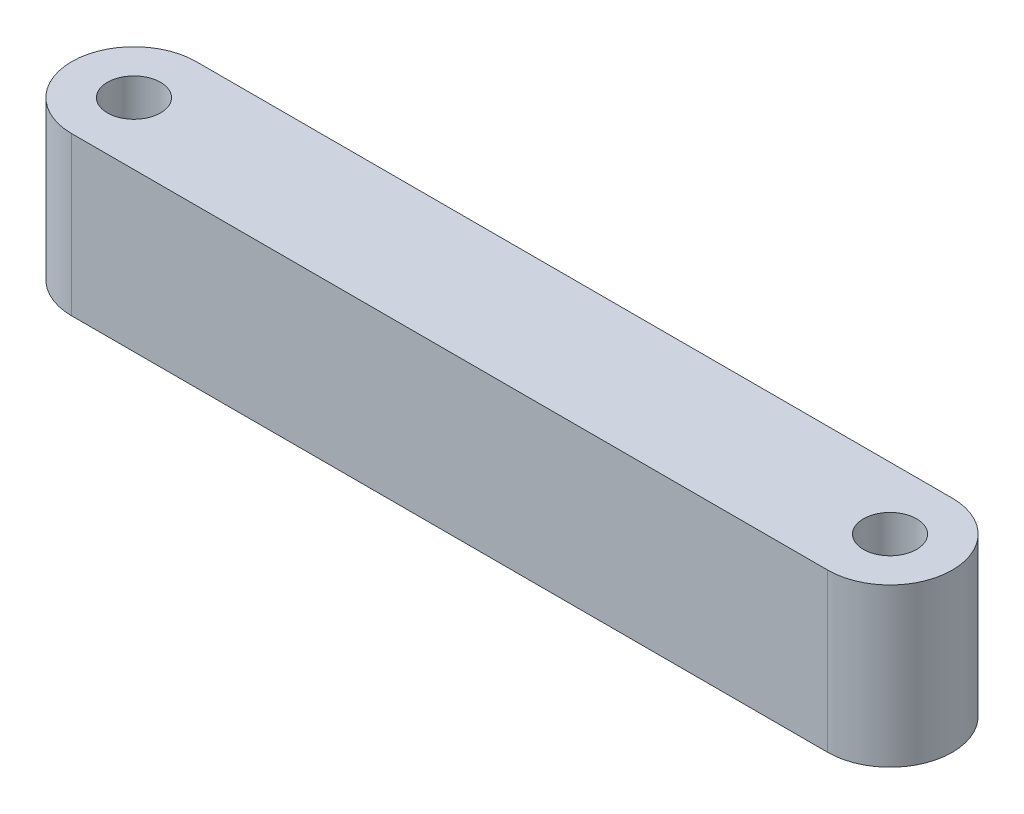
SolidWorks part; units mm, degrees
ref_plane "Alzado" through (0, 0, 0) normal (0, 0, 1) x (1, 0, 0)
ref_plane "Planta" through (0, 0, 0) normal (0, 1, 0) x (1, 0, 0)
ref_plane "Vista lateral" through (0, 0, 0) normal (1, 0, 0) x (0, 0, -1)
sketch "Croquis1" plane through (0, 0, 0) normal (0, 1, 0) x (1, 0, 0)
  line L1 (-26.5, -3.75) -> (26.5, -3.75)
  line L2 (-26.5, -3.75) -> (-26.5, 3.75)
  line L3 (-26.5, 3.75) -> (26.5, 3.75)
  line L4 (26.5, -3.75) -> (26.5, 3.75)
  line L5 (-26.5, -3.75) -> (26.5, 3.75) construction
  line L6 (-26.5, 3.75) -> (26.5, -3.75) construction
  point P0 (0, 0)
  dimension "D1" = 53
  dimension "D2" = 7.5
extrude "Saliente-Extruir1" add sketch "Croquis1" along normal blind 9.5
fillet "Redondeo1" 2 edges at (26.5, 4.75, -3.75) (26.5, 4.75, 3.75) type full round first side face at (0, 4.75, -3.75) second side face at (0, 4.75, 3.75) middle face at (26.5, 4.75, 0)
fillet "Redondeo3" 2 edges at (-26.5, 4.75, -3.75) (-26.5, 4.75, 3.75) type full round first side face at (-1.875, 4.75, -3.75) second side face at (-1.875, 4.75, 3.75) middle face at (-26.5, 4.75, 0)
sketch "Croquis2" plane through (0, 9.5, 0) normal (0, 1, 0) x (1, 0, 0)
  circle A0 centre (-22.75, 0) radius 1.6
  circle A1 centre (22.75, 0) radius 1.6
  dimension "D1" = 3.2
  dimension "D2" = 3.2
extrude "Cortar-Extruir1" cut sketch "Croquis2" against normal through all
